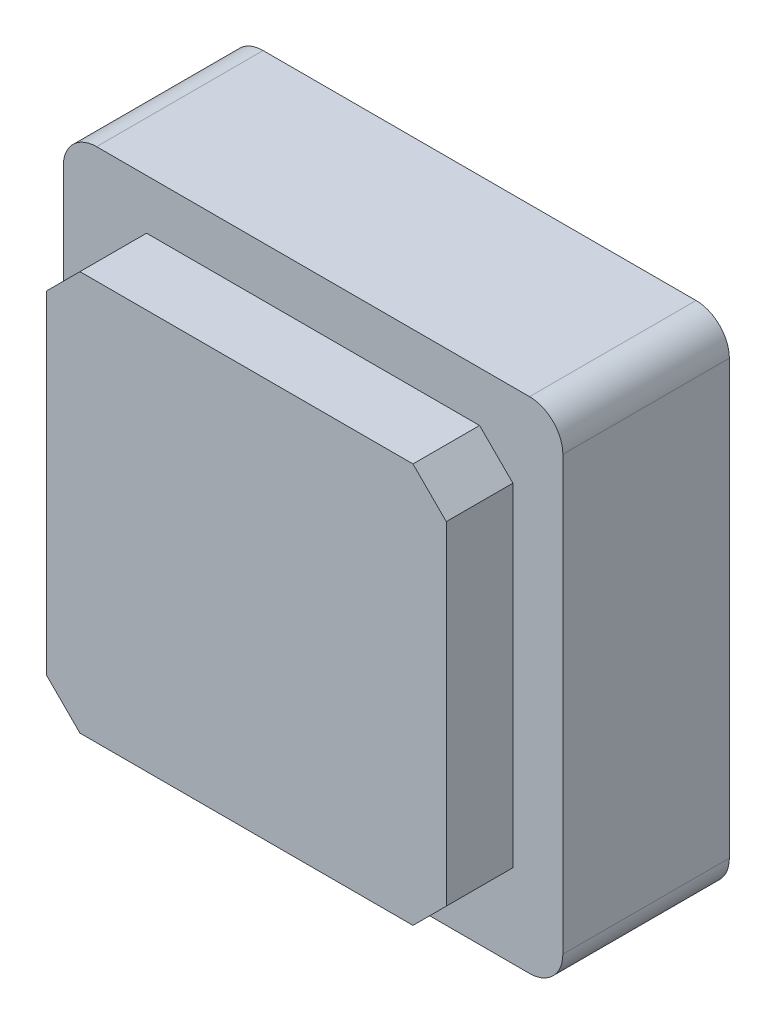
SolidWorks part; units mm, degrees
ref_plane "Plan de face" through (0, 0, 0) normal (0, 0, 1) x (1, 0, 0)
ref_plane "Plan de dessus" through (0, 0, 0) normal (0, 1, 0) x (1, 0, 0)
ref_plane "Plan de droite" through (0, 0, 0) normal (1, 0, 0) x (0, 0, -1)
sketch "Esquisse1" plane through (0, 0, 0) normal (0, 0, 1) x (1, 0, 0)
  line L1 (-7.5, -7.5) -> (7.5, -7.5)
  line L2 (-7.5, -7.5) -> (-7.5, 7.5)
  line L3 (-7.5, 7.5) -> (7.5, 7.5)
  line L4 (7.5, -7.5) -> (7.5, 7.5)
  line L5 (-7.5, -7.5) -> (7.5, 7.5) construction
  line L6 (-7.5, 7.5) -> (7.5, -7.5) construction
  point P0 (0, 0)
  dimension "D1" = 15
  dimension "D2" = 15
extrude "Boss.-Extru.1" add sketch "Esquisse1" along normal blind 5
fillet "Congé1" radius 1 4 edges at (-7.5, -7.5, 2.5) (7.5, -7.5, 2.5) (7.5, 7.5, 2.5) (-7.5, 7.5, 2.5)
sketch "Esquisse2" plane through (0, 0, 0) normal (0, 0, -1) x (-1, 0, 0)
  circle A0 centre (3.2609, 0) radius 1.5
  dimension "D1" = 3
extrude "Boss.-Extru.2" add sketch "Esquisse2" along normal blind 0.3
fillet "Congé2" radius 1 1 edges at (-4.7609, 0, -0.3)
sketch "Esquisse3" plane through (0, 0, 5) normal (0, 0, 1) x (1, 0, 0)
  circle A0 centre (6.5, 0) radius 0.65
  dimension "D1" = 1.3
  dimension "D2" = 6.5
extrude "Boss.-Extru.3" [suppressed] add sketch "Esquisse3" along normal blind 50
sketch "Esquisse4" plane through (0, 0, 5) normal (0, 0, 1) x (1, 0, 0)
  line L1 (-6, -6) -> (6, -6)
  line L2 (-6, -6) -> (-6, 6)
  line L3 (-6, 6) -> (6, 6)
  line L4 (6, -6) -> (6, 6)
  line L5 (-6, -6) -> (6, 6) construction
  line L6 (-6, 6) -> (6, -6) construction
  point P0 (0, 0)
  dimension "D1" = 12
  dimension "D2" = 12
extrude "Boss.-Extru.4" add sketch "Esquisse4" along normal blind 2
chamfer "Chanfrein1" distance 1 angle 45 4 edges at (-6, -6, 6) (6, -6, 6) (6, 6, 6) (-6, 6, 6)
